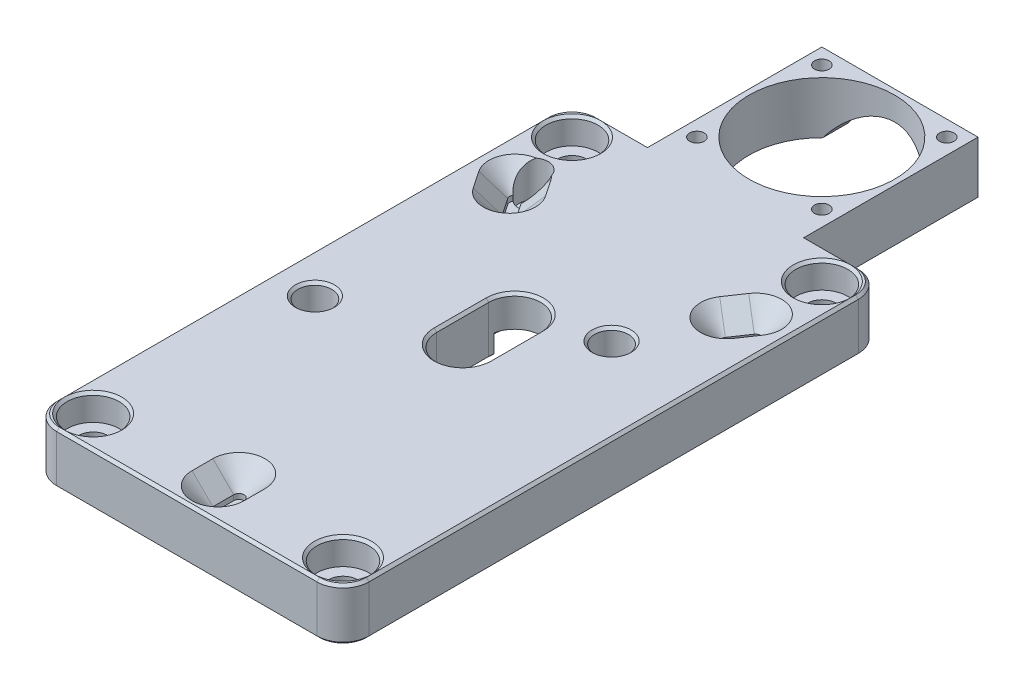
SolidWorks part; units mm, degrees
ref_plane "Front Plane" through (0, 0, 0) normal (0, 0, 1) x (1, 0, 0)
ref_plane "Top Plane" through (0, 0, 0) normal (0, 1, 0) x (1, 0, 0)
ref_plane "Right Plane" through (0, 0, 0) normal (1, 0, 0) x (0, 0, -1)
sketch "Sketch1" plane through (0, 0, 0) normal (0, 1, 0) x (1, 0, 0)
  line L1 (-30, 52) -> (30, 52)
  line L2 (-30, 52) -> (-30, -52)
  line L3 (-30, -52) -> (30, -52)
  line L4 (30, 52) -> (30, -52)
  line L5 (-30, 52) -> (30, -52) construction
  line L6 (-30, -52) -> (30, 52) construction
  point P0 (0, 0)
  dimension "D1" = 60
  dimension "D2" = 104
extrude "Boss-Extrude1" add sketch "Sketch1" along normal blind 10
sketch "Sketch10" plane through (0, 10, 0) normal (0, 1, 0) x (1, 0, 0)
  circle A0 centre (0, -44) radius 2.75 construction
  circle A1 centre (-22, 32.5) radius 2.75 construction
  circle A2 centre (22, 32.5) radius 2.75 construction
  circle A3 centre (0, -44) radius 2.75
  circle A4 centre (-22, 32.5) radius 2.75
  circle A5 centre (22, 32.5) radius 2.75
  circle A6 centre (0, 34) radius 15 construction
  circle A7 centre (0, -21.5) radius 15 construction
  circle A8 centre (0, 34) radius 15
  circle A9 centre (0, -21.5) radius 15
  circle A10 centre (0, 11) radius 1.85 construction
  circle A11 centre (0, 1) radius 1.85 construction
  circle A12 centre (0, 11) radius 1.85
  circle A13 centre (0, 1) radius 1.85
sketch "Sketch3" plane through (0, 10, 0) normal (0, 1, 0) x (1, 0, 0)
  line L0 (0, 0) -> (22, 32.5) construction
  line L1 (0, 0) -> (-22, 32.5) construction
  line L5 (0, 0) -> (0, -44) construction
  line L6 (-23.1211, 34.1562) -> (-20.8789, 30.8438) construction
  line L7 (-22.293, 34.7168) -> (-20.0508, 31.4043)
  line L8 (-23.9492, 33.5957) -> (-21.707, 30.2832)
  line L9 (23.1211, 34.1562) -> (20.8789, 30.8438) construction
  line L10 (23.9492, 33.5957) -> (21.707, 30.2832)
  line L11 (22.293, 34.7168) -> (20.0508, 31.4043)
  line L12 (0, -46) -> (0, -42) construction
  line L13 (-1, -46) -> (-1, -42)
  line L14 (1, -46) -> (1, -42)
  arc A0 (-22.293, 34.7168) -> (-23.9492, 33.5957) centre (-23.1211, 34.1562) ccw
  arc A1 (-21.707, 30.2832) -> (-20.0508, 31.4043) centre (-20.8789, 30.8438) ccw
  arc A2 (23.9492, 33.5957) -> (22.293, 34.7168) centre (23.1211, 34.1562) ccw
  arc A3 (20.0508, 31.4043) -> (21.707, 30.2832) centre (20.8789, 30.8438) ccw
  arc A4 (-1, -46) -> (1, -46) centre (0, -46) ccw
  arc A5 (1, -42) -> (-1, -42) centre (0, -42) ccw
  point P19 (-22, 32.5)
  point P25 (22, 32.5)
  point P32 (0, -44)
  dimension "D2" = 1
  dimension "D1" = 4
extrude "Cut-Extrude1" cut sketch "Sketch3" against normal blind 5
chamfer "Chamfer1" distance 4 angle 45 12 edges at (-22.8281, 10, -31.9394) (-20.3183, 10, -30.0157) (-23.6817, 10, -34.9843) (-21.1719, 10, -33.0606) (-1, 10, 44) (0, 10, 47) (0, 10, 41) (1, 10, 44) (21.1719, 10, -33.0606) (20.3183, 10, -30.0157) (23.6817, 10, -34.9843) (22.8281, 10, -31.9394)
sketch "Sketch5" plane through (0, 10, 0) normal (0, 1, 0) x (1, 0, 0)
  circle A2 centre (0, -21.5) radius 15 construction
  circle A3 centre (0, -21.5) radius 15
  circle A4 centre (0, 34) radius 15 construction
  circle A5 centre (0, 34) radius 15
extrude "Cut-Extrude3" cut sketch "Sketch5" against normal through all from offset 1.5 offset against normal yes
sketch "Sketch6" plane through (0, 10, 0) normal (0, 1, 0) x (1, 0, 0)
  line L8 (24, -46) -> (24, 46)
  line L9 (24, 46) -> (-24, 46)
  line L10 (-24, 46) -> (-24, -46)
  line L11 (-24, -46) -> (24, -46)
  line L12 (24, -46) -> (24, 46) construction
  line L13 (24, 46) -> (-24, 46) construction
  line L14 (-24, 46) -> (-24, -46) construction
  line L15 (-24, -46) -> (24, -46) construction
  dimension "D1" = 6
hole_wizard "CBORE for M5 SHCS1" positions "Sketch7" profile "Sketch8" counterbore size "M5" standard "ANSI Metric" end condition through all
sketch "Sketch7" plane through (0, 10, 0) normal (0, 1, 0) x (1, 0, 0)
  point P0 (-24, 46)
  point P3 (24, 46)
  point P6 (24, -46)
  point P9 (-24, -46)
sketch "Sketch8" plane through (-24, 10, -46) normal (1, 0, 0) x (0, 0, 1)
  line L0 (0, 0) -> (0, 10)
  line L1 (0, 10) -> (2.75, 10)
  line L3 (2.75, 10) -> (2.75, 5)
  line L4 (2.75, 5) -> (5, 5)
  line L5 (5, 5) -> (5, 0)
  line L7 (5, 0) -> (0, 0)
  line L11 (0, -6.35) -> (0, 107.95) construction
  dimension "Thru Hole Dia." = 5.5
  dimension "Thru Hole Depth" = 10
  dimension "C'Bore Dia." = 10
  dimension "C'Bore Depth" = 5
fillet "Fillet1" radius 5 4 edges at (30, 5, -52) (30, 5, 52) (-30, 5, 52) (-30, 5, -52)
sketch "Sketch9" plane through (0, 0, 0) normal (0, -1, 0) x (1, 0, 0)
  circle A0 centre (0, -19) radius 0.35
  circle A4 centre (0, -34) radius 15 construction
  dimension "D1" = 0.7
extrude "Boss-Extrude2" add sketch "Sketch9" against normal up to next
sketch "Sketch11" plane through (0, 0, 0) normal (0, -1, 0) x (1, 0, 0)
  circle A0 centre (0, 6.5) radius 0.35
  circle A1 centre (0, 21.5) radius 15 construction
  arc A2 (-0.35, -19.0041) -> (0.35, -19.0041) centre (0, -19) ccw construction
extrude "Boss-Extrude3" add sketch "Sketch11" against normal up to next contours A0
pattern_circular "CirPattern1" count 6 over 360 about axis through (0, 0, 21.5) along (0, 1, 0) of "Boss-Extrude3"
pattern_circular "CirPattern2" count 6 over 360 about axis through (0, 0, -34) along (0, 1, 0) of "Boss-Extrude2"
sketch "Sketch12" plane through (0, 10, 0) normal (0, 1, 0) x (1, 0, 0)
  line L0 (0, 1) -> (0, 11) construction
  line L1 (-5, 1) -> (-5, 11)
  line L2 (5, 1) -> (5, 11)
  arc A0 (-5, 1) -> (5, 1) centre (0, 1) ccw
  arc A1 (5, 11) -> (-5, 11) centre (0, 11) ccw
  point P4 (0, 6)
  dimension "D1" = 5
extrude "Cut-Extrude4" cut sketch "Sketch12" against normal through all
sketch "Sketch13" plane through (0, 0, 0) normal (0, -1, 0) x (1, 0, 0)
  line L0 (-29.5747, -105) -> (25.4932, -105) construction
  line L1 (25, -52) -> (-25, -52) construction
  line L2 (-25.25, -39.849) -> (16.75, -39.849) construction
  line L3 (-25.25, -39.849) -> (-25.25, 8.151) construction
  line L4 (-25.25, 8.151) -> (16.75, 8.151) construction
  line L5 (16.75, 8.151) -> (16.75, -39.849) construction
  line L6 (-25.25, 8.151) -> (16.75, -39.849) construction
  line L7 (13.75, -15.849) -> (-4.25, -15.849) construction
  line L8 (10.9984, 0.151) -> (10.9984, -31.849) construction
  point P6 (-22.25, -36.849)
  point P7 (-22.25, 5.151)
  point P10 (-4.25, -15.849)
  point P14 (13.75, -15.849)
  point P19 (10.9984, -15.849)
  dimension "D1" = 53
  dimension "D2" = 65.151
  dimension "D3" = 3
  dimension "D4" = 3
  dimension "D5" = 3
  dimension "D6" = 48
  dimension "D7" = 42
  dimension "D8" = 4.25
  dimension "D9" = 3
  dimension "D10" = 32
  dimension "D11" = 5.7516
sketch "Sketch14" plane through (0, 0, 0) normal (0, -1, 0) x (1, 0, 0)
  circle A0 centre (-4.25, -15.849) radius 4
  dimension "D1" = 8
extrude "Cut-Extrude5" cut sketch "Sketch14" against normal blind 4
sketch "Sketch15" plane through (0, 0, -52) normal (0, 0, -1) x (-1, 0, 0)
  line L0 (-25, 0) -> (25, 0) construction
  line L1 (0, 0) -> (0, -6) construction
  line L2 (8, 0) -> (-8, 0)
  line L3 (-25, 10) -> (25, 10) construction
  arc A0 (8, 0) -> (-8, 0) centre (0, -6) ccw
  circle A1 centre (0, -6) radius 11.25 construction
  point P7 (0, -17.25)
  dimension "D1" = 10
  dimension "D3" = 22.5
  dimension "D2" = 6
  dimension "D4" = 27.25
extrude "Cut-Extrude6" cut sketch "Sketch15" against normal up to next
hole_wizard "CBORE for M3 SHCS1" positions "Sketch17" profile "Sketch18" counterbore size "M3" standard "ANSI Metric" end condition through all
sketch "Sketch17" plane through (0, 10, 0) normal (0, 1, 0) x (1, 0, 0)
  point P1 (-22.25, -5.151)
  point P5 (13.75, 15.849)
sketch "Sketch18" plane through (-22.25, 10, 5.151) normal (1, 0, 0) x (0, 0, 1)
  line L0 (0, 0) -> (0, 10)
  line L1 (0, 10) -> (1.7, 10)
  line L3 (1.7, 10) -> (1.7, 7)
  line L4 (1.7, 7) -> (3.25, 7)
  line L5 (3.25, 7) -> (3.25, 0)
  line L7 (3.25, 0) -> (0, 0)
  line L11 (0, -6.35) -> (0, 107.95) construction
  dimension "Thru Hole Dia." = 3.4
  dimension "Thru Hole Depth" = 10
  dimension "C'Bore Dia." = 6.5
  dimension "C'Bore Depth" = 7
sketch "Sketch22" plane through (0, 0, -52) normal (0, 0, -1) x (-1, 0, 0)
  line L0 (-25, 10) -> (25, 10) construction
  line L1 (15, 10) -> (-15, 10)
  line L2 (15, 10) -> (15, 0)
  line L4 (-15, 10) -> (-15, 0)
  line L6 (0, -6) -> (0, 10) construction
  line L7 (-9.8107, 0) -> (-15, 0)
  line L8 (-25, 0) -> (-8, 0) construction
  line L9 (9.8107, 0) -> (15, 0)
  line L10 (8, 0) -> (25, 0) construction
  arc A0 (8, 0) -> (-8, 0) centre (0, -6) ccw construction
  arc A1 (9.8107, 0) -> (-9.8107, 0) centre (0, -6) ccw
  point P6 (0, -6)
  dimension "D2" = 11.5
  dimension "D1" = 30
extrude "Boss-Extrude4" add sketch "Sketch22" along normal blind 33
sketch "Sketch23" plane through (0, 0, 0) normal (0, -1, 0) x (1, 0, 0)
  line L2 (-15, -85) -> (15, -85) construction
  line L3 (-12, -58) -> (12, -58) construction
  line L4 (-12, -58) -> (-12, -82) construction
  line L5 (-12, -82) -> (12, -82) construction
  line L6 (12, -58) -> (12, -82) construction
  line L7 (-12, -58) -> (12, -82) construction
  line L8 (-12, -82) -> (12, -58) construction
  line L9 (15, -85) -> (15, -52) construction
  circle A0 centre (0, -70) radius 14
  circle A1 centre (-12, -58) radius 1.4
  circle A2 centre (12, -58) radius 1.4
  circle A3 centre (12, -82) radius 1.4
  circle A4 centre (-12, -82) radius 1.4
  dimension "D1" = 28
  dimension "D5" = 2.8
  dimension "D2" = 15
  dimension "D3" = 15
  dimension "D4" = 24
extrude "Cut-Extrude10" cut sketch "Sketch23" against normal through all
chamfer "Chamfer2" distance 0.5 angle 45 35 edges at (0, 0, 52) (28.5355, 0, 50.5355) (-28.5355, 0, 50.5355) (30, 0, 0) (-30, 0, 0) (28.5355, 0, -50.5355) (-28.5355, 0, -50.5355) (20, 0, -52) (-20, 0, -52) (-5, 0, -6) (0, 0, 4) (-4.9793, 0, -11.4544) (3.4451, 0, -14.6237) (5, 0, -6) (24, 10, 51) (-24, 10, 51) (-24, 10, -41) (24, 10, -41) (-5, 10, -6) (0, 10, 4) (0, 10, -16) (5, 10, -6) (-30, 10, 0) (-28.5355, 10, 50.5355) (-28.5355, 10, -50.5355) (0, 10, 52) (20, 10, -52) (-20, 10, -52) (28.5355, 10, 50.5355) (28.5355, 10, -50.5355) (30, 10, 0) (-22.25, 10, 8.401) (13.75, 10, -12.599) (-8.2498, 0, -15.8852) (-0.7372, 0, -17.7621)
sketch "Sketch19" plane through (0, 10, 0) normal (0, 1, 0) x (1, 0, 0)
  circle A0 centre (-22.25, 36.849) radius 2.8
  dimension "D1" = 5.6
extrude "Cut-Extrude8" cut sketch "Sketch19" against normal up to surface (7 mm away) contours A0 up to face at (13.75, 3, -14.149)
sketch "Sketch20" plane through (0, 3, 0) normal (0, 1, 0) x (1, 0, 0)
  circle A0 centre (-22.25, 36.849) radius 1.6
  circle A1 centre (-22.25, 36.849) radius 2.8 construction
  dimension "D1" = 3.2
extrude "Cut-Extrude9" cut sketch "Sketch20" against normal through all
